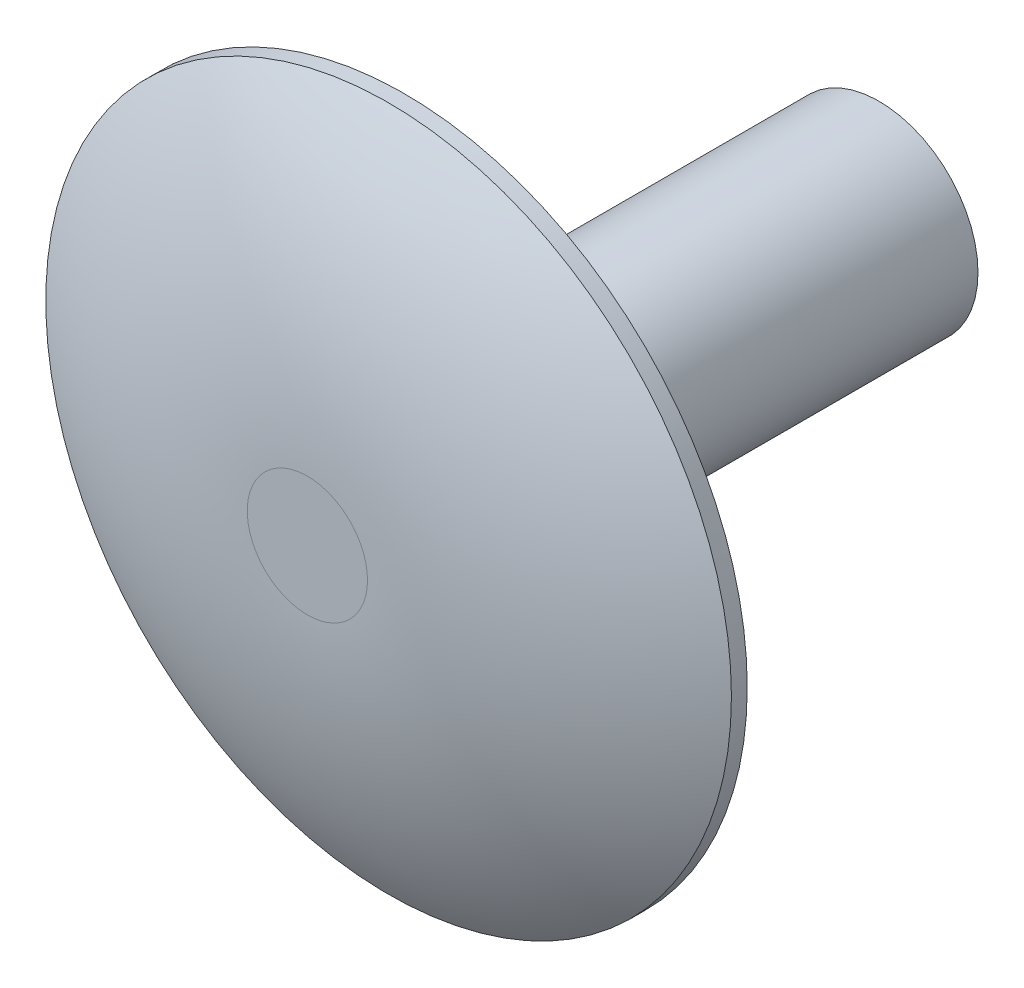
SolidWorks part; units mm, degrees
material "6061 Alloy"
ref_plane "Front Plane" through (0, 0, 0) normal (0, 0, 1) x (1, 0, 0)
ref_plane "Top Plane" through (0, 0, 0) normal (0, 1, 0) x (1, 0, 0)
ref_plane "Right Plane" through (0, 0, 0) normal (1, 0, 0) x (0, 0, -1)
sketch "Sketch1" plane through (0, 0, 0) normal (0, 0, 1) x (1, 0, 0)
  circle A0 centre (0, 0) radius 8.255
  dimension "D1" = 16.51
extrude "Boss-Extrude1" add sketch "Sketch1" along normal blind 2.3368
sketch "Sketch2" plane through (0, 0, 0) normal (0, 0, 1) x (1, 0, 0)
  circle A0 centre (0, 0) radius 2.3813
  dimension "D1" = 4.7625
extrude "Boss-Extrude2" add sketch "Sketch2" against normal blind 11.43
sketch "Sketch3" plane through (0, 0, 0) normal (0, 1, 0) x (1, 0, 0)
  line L0 (0, -2.3368) -> (1.4478, -2.3368)
  line L1 (-8.255, -2.3368) -> (8.255, -2.3368) construction
  line L2 (0, -2.3368) -> (0, 0) construction
  line L3 (8.255, -2.3368) -> (8.255, 0) construction
  line L4 (8.255, -0.381) -> (8.255, 0)
  line L5 (8.255, 0) -> (-8.255, 0) construction
  line L6 (8.255, -0.381) -> (8.255, -2.3368)
  line L7 (8.255, -2.3368) -> (1.4478, -2.3368)
  arc A0 (1.4478, -2.3368) -> (8.255, -0.381) centre (1.4478, 10.4874) ccw
  dimension "D1" = 2.8956
  dimension "D2" = 0.381
revolve "Cut-Revolve1" cut sketch "Sketch3" angle 360 about L2 region at (6.5802, 0, 1.7586)
